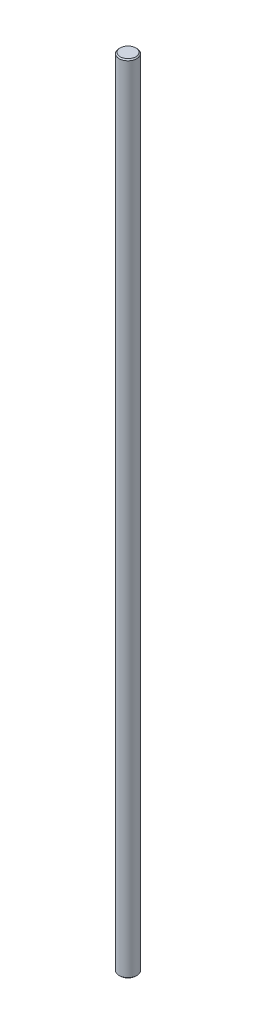
SolidWorks part; units mm, degrees
ref_plane "Front Plane" through (0, 0, 0) normal (0, 0, 1) x (1, 0, 0)
ref_plane "Top Plane" through (0, 0, 0) normal (0, 1, 0) x (1, 0, 0)
ref_plane "Right Plane" through (0, 0, 0) normal (1, 0, 0) x (0, 0, -1)
sketch "Sketch1" plane through (0, 0, 0) normal (0, 1, 0) x (1, 0, 0)
  circle A0 centre (0, 0) radius 4
  dimension "D1" = 8
extrude "Boss-Extrude1" add sketch "Sketch1" along normal blind 180 and the other way blind 180
chamfer "Chamfer1" distance 0.5 angle 45 2 edges at (0, -180, 4) (0, 180, 4)
